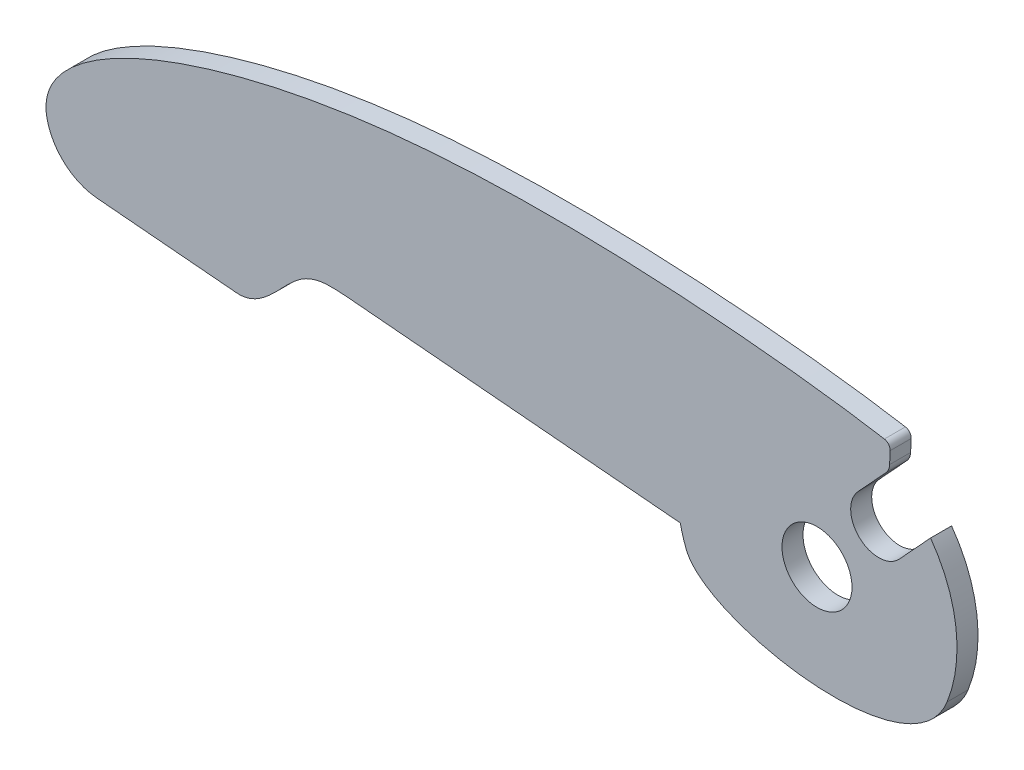
SolidWorks part; units mm, degrees
ref_plane "Přední rovina" through (0, 0, 0) normal (0, 0, 1) x (1, 0, 0)
ref_plane "Horní rovina" through (0, 0, 0) normal (0, 1, 0) x (1, 0, 0)
ref_plane "Pravá rovina" through (0, 0, 0) normal (1, 0, 0) x (0, 0, -1)
sketch "Skica1" plane through (0, 0, 0) normal (0, 0, 1) x (1, 0, 0)
  line L0 (-8.1842, -2.2954) -> (-9.7646, -2.1572) construction
  line L2 (0, 0) -> (-59.5409, 0) construction
  line L3 (0, 0) -> (14.9629, 16.2348) construction
  line L4 (5.2255, 9.8063) -> (5.1859, 8.9247)
  line L5 (2.9345, 6.135) -> (4.9223, 8.2918)
  line L7 (-9.7646, -2.1572) -> (-33.4565, -0.0844)
  line L8 (-41.4565, -3.7694) -> (12.003, -8.4465) construction
  line L9 (5.8758, 3.4242) -> (8.1109, 5.8492)
  line L12 (-51.4184, -2.8978) -> (-41.4565, -3.7694)
  circle A0 centre (0, 0) radius 2.5
  arc A1 (9.2885, -3.7045) -> (8.1109, 5.8492) centre (0, 0) ccw
  arc A2 (9.1735, 3.9807) -> (0, 10) centre (0, 0) ccw construction
  arc A3 (-55, 0.324) -> (-51.4184, -2.8978) centre (-51.0735, 1.0873) ccw construction
  arc A4 (5.7606, 6.2503) -> (3.0497, 3.309) centre (4.4051, 4.7796) ccw construction
  arc A5 (2.9345, 6.135) -> (5.8758, 3.4242) centre (4.4051, 4.7796) ccw
  arc A6 (4.8128, 10.3211) -> (5.2255, 9.8063) centre (4.726, 9.8287) cw
  arc A9 (-55, 0.324) -> (-51.4184, -2.8978) centre (-51.0735, 1.0873) ccw
  arc A11 (5.1859, 8.9247) -> (4.9223, 8.2918) centre (4.1869, 8.9695) cw
  arc A14 (-9.7646, -2.1572) -> (-1.9081, -9.8163) centre (0, 0) ccw construction
  arc A15 (-9.7646, -2.1572) -> (-9.342, -3.5676) centre (0, 0) ccw
  spline S1 degree 3 poles (9.2885, -3.7045) (6.8189, -9.8969) (-7.9149, -7.3044) (-9.342, -3.5676) knots 0 0 0 0 1 1 1 1
  spline S2 degree 3 poles (-1925.6741, 531.881) (198.0272, -87.1071) (-87.3625, 121.314) (-123.6185, -107.1553) (1933.4633, 201.1585) knots -2.379902 -2.379902 -2.379902 -2.379902 0.525666 3.18751 3.18751 3.18751 3.18751 only from (4.8128, 10.3211) to (-55, 0.324) construction
  spline S3 degree 3 poles (4.8128, 10.3211) (-0.4395, 11.2472) (-32.098, 15.081) (-55.954, 5.2322) (-55, 0.324) knots 0 0 0 0 0.525666 0.98526 0.98526 0.98526 0.98526
  spline S4 degree 3 poles (-41.4565, -3.7694) (-39.7961, -3.9146) (-37.0548, 0.0644) (-35.1168, 0.0609) (-33.4565, -0.0844) knots 0 0 0 0 0.457393 1 1 1 1
  point P36 (5.1696, 8.5601)
  dimension "D1" = 5
  dimension "D2" = 10
  dimension "D3" = 5
  dimension "D4" = 5
  dimension "D6" = 3
  dimension "D7" = 8
  dimension "D10" = 1
  dimension "D11" = 20
  dimension "D13" = 3
  dimension "D12" = 12
  dimension "D9" = 4
  dimension "D8" = 0.5
extrude "Přidat vysunutím1" add sketch "Skica1" along normal mid plane 1.5
